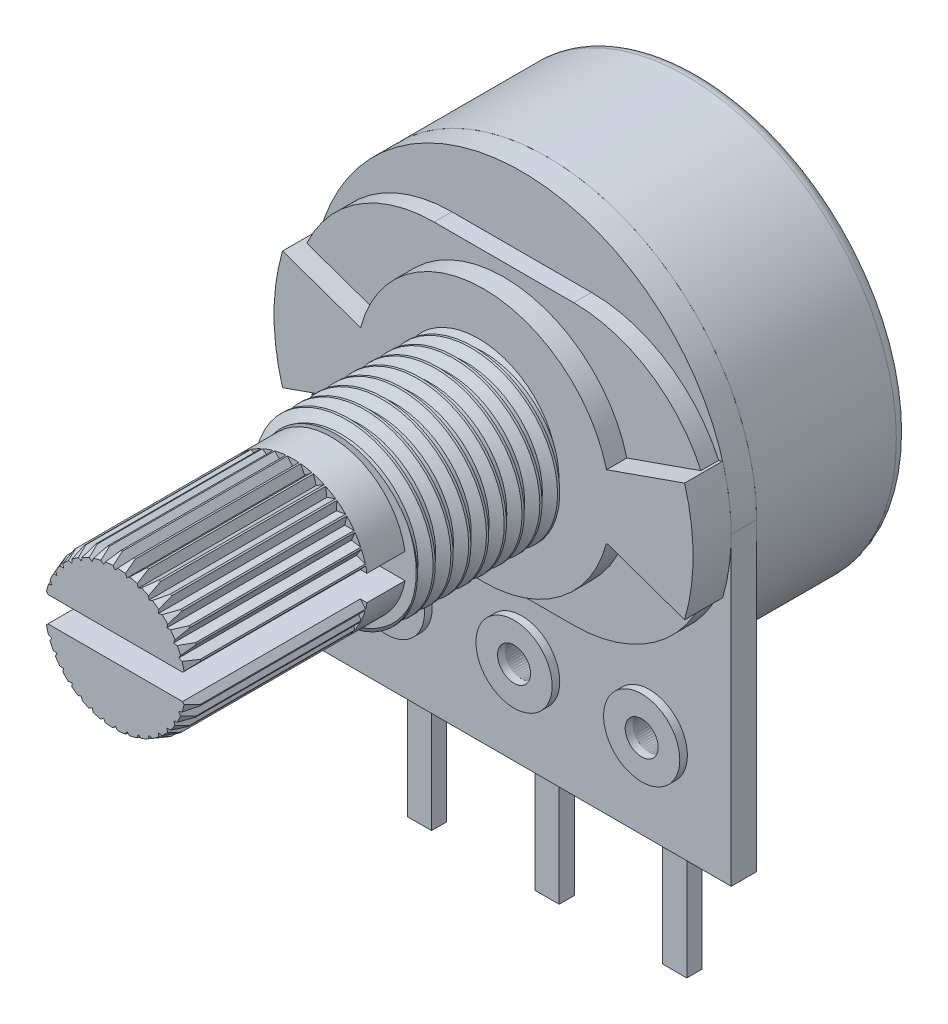
SolidWorks part; units mm, degrees
ref_plane "Front Plane" through (0, 0, 0) normal (0, 0, 1) x (1, 0, 0)
ref_plane "Top Plane" through (0, 0, 0) normal (0, 1, 0) x (1, 0, 0)
ref_plane "Right Plane" through (0, 0, 0) normal (1, 0, 0) x (0, 0, -1)
sketch "Sketch1" plane through (0, 0, 0) normal (0, 0, 1) x (1, 0, 0)
  circle A0 centre (0, 0) radius 8.25
  dimension "D1" = 16.5
extrude "Boss-Extrude1" add sketch "Sketch1" along normal blind 6
sketch "Sketch2" plane through (0, 0, 6) normal (0, 0, 1) x (1, 0, 0)
  line L0 (-8.25, 0) -> (-8.25, -12)
  line L1 (-8.25, -12) -> (8.25, -12)
  line L2 (8.25, -12) -> (8.25, 0)
  circle A1 centre (0, 0) radius 8.25
  arc A2 (8.25, 0) -> (-8.25, 0) centre (0, 0) ccw
  dimension "D2" = 12
  dimension "D1" = 0
extrude "Boss-Extrude2" add sketch "Sketch2" along normal blind 1 separate body
sketch "Sketch3" plane through (0, 0, 6) normal (0, 0, -1) x (-1, 0, 0)
  line L0 (8.25, -12) -> (-8.25, -12) construction
  line L1 (0.475, -12.7) -> (0.475, -17)
  line L2 (-0.475, -12.7) -> (-0.475, -17)
  line L3 (0.3, -6.9) -> (-0.3, -6.9)
  line L4 (0.475, -17) -> (-0.475, -17)
  line L5 (0.475, -12.7) -> (1.8, -12.7)
  line L6 (1.8, -8.4) -> (1.8, -12.7)
  line L7 (5.5, -12.7) -> (5.5, -17)
  line L8 (4.55, -12.7) -> (4.55, -17)
  line L9 (8.25, -12) -> (-8.25, -12) construction
  line L10 (5.325, -6.9) -> (4.725, -6.9)
  line L11 (-1.8, -8.4) -> (-1.8, -12.7)
  line L12 (-0.475, -12.7) -> (-1.8, -12.7)
  line L13 (0, -17) -> (0, -9.9633) construction
  line L14 (0.9971, -13.9354) -> (-0.3886, -13.9354) construction
  line L15 (5.5, -17) -> (4.55, -17)
  line L16 (-1.1375, -10.55) -> (-1.8, -10.55) construction
  line L17 (5.025, -17) -> (5.025, -9.9633) construction
  line L18 (6.0221, -13.9354) -> (4.6364, -13.9354) construction
  line L19 (3.8875, -10.55) -> (3.225, -10.55) construction
  line L20 (1.1375, -12.7) -> (1.1375, -9.9633) construction
  line L21 (1.6718, -10.55) -> (1.8, -10.55) construction
  line L22 (5.5, -12.7) -> (6.825, -12.7)
  line L23 (6.825, -8.4) -> (6.825, -12.7)
  line L24 (6.1625, -12.7) -> (6.1625, -9.9633) construction
  line L25 (6.6968, -10.55) -> (6.825, -10.55) construction
  line L26 (3.8875, -12.7) -> (3.8875, -9.9633) construction
  line L27 (3.225, -8.4) -> (3.225, -12.7)
  line L28 (4.55, -12.7) -> (3.225, -12.7)
  line L29 (-1.1375, -12.7) -> (-1.1375, -9.9633) construction
  line L30 (-4.55, -12.7) -> (-4.55, -17)
  line L33 (-5.5, -12.7) -> (-5.5, -17)
  line L35 (-4.725, -6.9) -> (-5.325, -6.9)
  line L36 (-4.55, -17) -> (-5.5, -17)
  line L37 (-4.55, -12.7) -> (-3.225, -12.7)
  line L38 (-3.225, -8.4) -> (-3.225, -12.7)
  line L39 (-6.825, -8.4) -> (-6.825, -12.7)
  line L40 (-5.5, -12.7) -> (-6.825, -12.7)
  line L41 (-5.025, -17) -> (-5.025, -9.9633) construction
  line L42 (-4.0279, -13.9354) -> (-5.4136, -13.9354) construction
  line L43 (-6.1625, -10.55) -> (-6.825, -10.55) construction
  line L44 (-3.8875, -12.7) -> (-3.8875, -9.9633) construction
  line L45 (-3.3532, -10.55) -> (-3.225, -10.55) construction
  line L46 (-6.1625, -12.7) -> (-6.1625, -9.9633) construction
  arc A0 (3.225, -8.4) -> (4.725, -6.9) centre (4.725, -8.4) cw
  arc A1 (5.325, -6.9) -> (6.825, -8.4) centre (5.325, -8.4) cw
  arc A2 (-1.8, -8.4) -> (-0.3, -6.9) centre (-0.3, -8.4) cw
  arc A3 (0.3, -6.9) -> (1.8, -8.4) centre (0.3, -8.4) cw
  arc A4 (-6.825, -8.4) -> (-5.325, -6.9) centre (-5.325, -8.4) cw
  arc A5 (-4.725, -6.9) -> (-3.225, -8.4) centre (-4.725, -8.4) cw
  circle A6 centre (5.025, -8.4) radius 0.65
  circle A7 centre (0, -8.4) radius 0.65
  circle A8 centre (-5.025, -8.4) radius 0.65
  point P18 (3.225, -6.9)
  point P24 (6.825, -6.9)
  point P34 (3.8875, -10.55)
  point P41 (-1.1375, -10.55)
  point P46 (0, -13.9354)
  point P51 (1.1375, -10.55)
  point P68 (-6.1625, -10.55)
  point P73 (-5.025, -13.9354)
  point P78 (-3.8875, -10.55)
  point P114 (5.025, -13.9354)
  point P176 (6.1625, -10.55)
  dimension "D7" = 1.5
  dimension "D10" = 1.3
  dimension "D1" = 5
  dimension "D3" = 0.7
  dimension "D4" = 0.95
  dimension "D5" = 3.6
  dimension "D6" = 5.1
  dimension "D8" = 11
  dimension "D9" = 3.6
  dimension "D2" = 3
extrude "Boss-Extrude3" add sketch "Sketch3" along normal blind 0.6 separate body
sketch "Sketch4" plane through (0, 0, 7) normal (0, 0, 1) x (1, 0, 0)
  line L0 (0, 0) -> (-8.25, 0) construction
  line L1 (-7.9141, 2.33) -> (-4.8412, 1.25)
  line L2 (-7.9141, -2.33) -> (-4.8412, -1.25)
  line L3 (0, 0) -> (0, 10.6745) construction
  line L4 (7.9141, -2.33) -> (4.8412, -1.25)
  line L5 (7.9141, 2.33) -> (4.8412, 1.25)
  arc A0 (-4.8412, -1.25) -> (4.8412, -1.25) centre (0, 0) ccw
  arc A2 (-7.9141, 2.33) -> (-7.9141, -2.33) centre (0, 0) ccw
  arc A3 (7.9141, 2.33) -> (7.9141, -2.33) centre (0, 0) cw
  arc A4 (4.8412, 1.25) -> (-4.8412, 1.25) centre (0, 0) ccw
  dimension "D1" = 10
  dimension "D2" = 4.66
  dimension "D3" = 2.5
extrude "Boss-Extrude4" add sketch "Sketch4" along normal blind 1.5 separate body
sketch "Sketch15" plane through (0, 0, 7) normal (0, 0, 1) x (1, 0, 0)
  line L0 (2.75, 0) -> (-2.75, 0) construction
  line L1 (2.75, -5.5) -> (-2.75, -5.5)
  line L2 (2.75, 5.5) -> (-2.75, 5.5)
  line L3 (-8.25, 0) -> (-8.25, -12) construction
  arc A0 (2.75, -5.5) -> (2.75, 5.5) centre (2.75, 0) ccw
  arc A1 (-2.75, 5.5) -> (-2.75, -5.5) centre (-2.75, 0) ccw
  point P2 (0, 0)
  dimension "D1" = 11
extrude "Boss-Extrude8" add sketch "Sketch15" along normal blind 0.7
sketch "Sketch5" plane through (0, 0, 8.5) normal (0, 0, 1) x (1, 0, 0)
  circle A0 centre (0, 0) radius 3.35
  dimension "D1" = 6.7
extrude "Boss-Extrude5" add sketch "Sketch5" along normal blind 6
sketch "Sketch6" plane through (0, 0, 14.5) normal (0, 0, 1) x (1, 0, 0)
  line L0 (0, 0) -> (-1.7452, 0) construction
  line L1 (-2.9073, 0.5) -> (2.9073, 0.5)
  line L2 (-2.9073, -0.5) -> (2.9073, -0.5)
  circle A0 centre (0, 0) radius 3.35 construction
  arc A1 (2.9073, 0.5) -> (-2.9073, 0.5) centre (0, 0) ccw
  arc A3 (-2.9073, -0.5) -> (2.9073, -0.5) centre (0, 0) ccw
  dimension "D1" = 5.9
  dimension "D2" = 1
extrude "Boss-Extrude6" add sketch "Sketch6" along normal blind 8.5
thread "Thread1" pitch 0.7 method cut profile "Thread Profile1" start angle 0, offset 1, length 7, pitch 0.7, diameter 6.7
ref_plane "Plane1" through (-3.35, 0, 15.5) normal (0, -1, 0) x (-1, 0, 0)
sketch "Thread Profile1" plane through (-3.35, 0, 15.5) normal (0, -1, 0) x (-1, 0, 0)
  line L0 (0, 0) -> (0, 0.7) construction
  line L11 (0, 0) -> (0, 0.6125)
  line L12 (0, 0.6125) -> (-0.3789, 0.3937)
  line L13 (-0.3789, 0.3937) -> (-0.3789, 0.2187)
  line L15 (-0.3789, 0.2187) -> (0, 0)
  line L17 (-0.3789, 0.3062) -> (0, 0.3062) construction
  point P2 (0, 0)
  dimension "Pitch" = 0.7
  dimension "Profile_Angle" = 60
  dimension "Profile_Land" = 0.175
  dimension "Profile_Height" = 0.3789
chamfer "Chamfer1" distance 0.5 angle 20 2 edges at (0, -2.95, 23) (0, 2.95, 23) first distance on face at (0, -1.725, 18.75) first distance on face at (0, 1.725, 18.75)
sketch "Sketch10" plane through (0, 0, 23) normal (0, 0, 1) x (1, 0, 0)
  line L0 (0, 0) -> (0, 2.95) construction
  line L1 (-0.2382, 2.9681) -> (0, 2.6569)
  line L2 (0, 2.6569) -> (0.255, 2.9668)
  line L3 (0.255, 2.9668) -> (-0.2382, 2.9681)
  line L4 (0.7663, 2.8774) -> (0.2808, 2.9643)
  line L5 (0.4614, 2.6166) -> (0.7663, 2.8774)
  line L6 (0.2808, 2.9643) -> (0.4614, 2.6166)
  line L7 (1.2543, 2.7006) -> (0.7913, 2.8705)
  line L8 (0.9087, 2.4967) -> (1.2543, 2.7006)
  line L9 (0.7913, 2.8705) -> (0.9087, 2.4967)
  line L10 (1.7042, 2.4418) -> (1.2778, 2.6895)
  line L11 (1.3285, 2.301) -> (1.7042, 2.4418)
  line L12 (1.2778, 2.6895) -> (1.3285, 2.301)
  line L13 (2.1024, 2.1088) -> (1.7254, 2.4268)
  line L14 (1.7078, 2.0353) -> (2.1024, 2.1088)
  line L15 (1.7254, 2.4268) -> (1.7078, 2.0353)
  line L16 (2.4366, 1.7117) -> (2.1206, 2.0903)
  line L17 (2.0353, 1.7078) -> (2.4366, 1.7117)
  line L18 (2.1206, 2.0903) -> (2.0353, 1.7078)
  line L19 (2.6968, 1.2626) -> (2.4513, 1.6903)
  line L20 (2.301, 1.3285) -> (2.6968, 1.2626)
  line L21 (2.4513, 1.6903) -> (2.301, 1.3285)
  line L22 (2.8751, 0.7751) -> (2.7076, 1.239)
  line L23 (2.4967, 0.9087) -> (2.8751, 0.7751)
  line L24 (2.7076, 1.239) -> (2.4967, 0.9087)
  line L25 (2.966, 0.2641) -> (2.8816, 0.75)
  line L26 (2.6166, 0.4614) -> (2.966, 0.2641)
  line L27 (2.8816, 0.75) -> (2.6166, 0.4614)
  line L28 (2.9668, -0.255) -> (2.9681, 0.2382)
  line L29 (2.6569, 0) -> (2.9668, -0.255)
  line L30 (2.9681, 0.2382) -> (2.6569, 0)
  line L31 (2.8774, -0.7663) -> (2.9643, -0.2808)
  line L32 (2.6166, -0.4614) -> (2.8774, -0.7663)
  line L33 (2.9643, -0.2808) -> (2.6166, -0.4614)
  line L34 (2.7006, -1.2543) -> (2.8705, -0.7913)
  line L35 (2.4967, -0.9087) -> (2.7006, -1.2543)
  line L36 (2.8705, -0.7913) -> (2.4967, -0.9087)
  line L37 (2.4418, -1.7042) -> (2.6895, -1.2778)
  line L38 (2.301, -1.3285) -> (2.4418, -1.7042)
  line L39 (2.6895, -1.2778) -> (2.301, -1.3285)
  line L40 (2.1088, -2.1024) -> (2.4268, -1.7254)
  line L41 (2.0353, -1.7078) -> (2.1088, -2.1024)
  line L42 (2.4268, -1.7254) -> (2.0353, -1.7078)
  line L43 (1.7117, -2.4366) -> (2.0903, -2.1206)
  line L44 (1.7078, -2.0353) -> (1.7117, -2.4366)
  line L45 (2.0903, -2.1206) -> (1.7078, -2.0353)
  line L46 (1.2626, -2.6968) -> (1.6903, -2.4513)
  line L47 (1.3285, -2.301) -> (1.2626, -2.6968)
  line L48 (1.6903, -2.4513) -> (1.3285, -2.301)
  line L49 (0.7751, -2.8751) -> (1.239, -2.7076)
  line L50 (0.9087, -2.4967) -> (0.7751, -2.8751)
  line L51 (1.239, -2.7076) -> (0.9087, -2.4967)
  line L52 (0.2641, -2.966) -> (0.75, -2.8816)
  line L53 (0.4614, -2.6166) -> (0.2641, -2.966)
  line L54 (0.75, -2.8816) -> (0.4614, -2.6166)
  line L55 (-0.255, -2.9668) -> (0.2382, -2.9681)
  line L56 (0, -2.6569) -> (-0.255, -2.9668)
  line L57 (0.2382, -2.9681) -> (0, -2.6569)
  line L58 (-0.7663, -2.8774) -> (-0.2808, -2.9643)
  line L59 (-0.4614, -2.6166) -> (-0.7663, -2.8774)
  line L60 (-0.2808, -2.9643) -> (-0.4614, -2.6166)
  line L61 (-1.2543, -2.7006) -> (-0.7913, -2.8705)
  line L62 (-0.9087, -2.4967) -> (-1.2543, -2.7006)
  line L63 (-0.7913, -2.8705) -> (-0.9087, -2.4967)
  line L64 (-1.7042, -2.4418) -> (-1.2778, -2.6895)
  line L65 (-1.3285, -2.301) -> (-1.7042, -2.4418)
  line L66 (-1.2778, -2.6895) -> (-1.3285, -2.301)
  line L67 (-2.1024, -2.1088) -> (-1.7254, -2.4268)
  line L68 (-1.7078, -2.0353) -> (-2.1024, -2.1088)
  line L69 (-1.7254, -2.4268) -> (-1.7078, -2.0353)
  line L70 (-2.4366, -1.7117) -> (-2.1206, -2.0903)
  line L71 (-2.0353, -1.7078) -> (-2.4366, -1.7117)
  line L72 (-2.1206, -2.0903) -> (-2.0353, -1.7078)
  line L73 (-2.6968, -1.2626) -> (-2.4513, -1.6903)
  line L74 (-2.301, -1.3285) -> (-2.6968, -1.2626)
  line L75 (-2.4513, -1.6903) -> (-2.301, -1.3285)
  line L76 (-2.8751, -0.7751) -> (-2.7076, -1.239)
  line L77 (-2.4967, -0.9087) -> (-2.8751, -0.7751)
  line L78 (-2.7076, -1.239) -> (-2.4967, -0.9087)
  line L79 (-2.966, -0.2641) -> (-2.8816, -0.75)
  line L80 (-2.6166, -0.4614) -> (-2.966, -0.2641)
  line L81 (-2.8816, -0.75) -> (-2.6166, -0.4614)
  line L82 (-2.9668, 0.255) -> (-2.9681, -0.2382)
  line L83 (-2.6569, 0) -> (-2.9668, 0.255)
  line L84 (-2.9681, -0.2382) -> (-2.6569, 0)
  line L85 (-2.8774, 0.7663) -> (-2.9643, 0.2808)
  line L86 (-2.6166, 0.4614) -> (-2.8774, 0.7663)
  line L87 (-2.9643, 0.2808) -> (-2.6166, 0.4614)
  line L88 (-2.7006, 1.2543) -> (-2.8705, 0.7913)
  line L89 (-2.4967, 0.9087) -> (-2.7006, 1.2543)
  line L90 (-2.8705, 0.7913) -> (-2.4967, 0.9087)
  line L91 (-2.4418, 1.7042) -> (-2.6895, 1.2778)
  line L92 (-2.301, 1.3285) -> (-2.4418, 1.7042)
  line L93 (-2.6895, 1.2778) -> (-2.301, 1.3285)
  line L94 (-2.1088, 2.1024) -> (-2.4268, 1.7254)
  line L95 (-2.0353, 1.7078) -> (-2.1088, 2.1024)
  line L96 (-2.4268, 1.7254) -> (-2.0353, 1.7078)
  line L97 (-1.7117, 2.4366) -> (-2.0903, 2.1206)
  line L98 (-1.7078, 2.0353) -> (-1.7117, 2.4366)
  line L99 (-2.0903, 2.1206) -> (-1.7078, 2.0353)
  line L100 (-1.2626, 2.6968) -> (-1.6903, 2.4513)
  line L101 (-1.3285, 2.301) -> (-1.2626, 2.6968)
  line L102 (-1.6903, 2.4513) -> (-1.3285, 2.301)
  line L103 (-0.7751, 2.8751) -> (-1.239, 2.7076)
  line L104 (-0.9087, 2.4967) -> (-0.7751, 2.8751)
  line L105 (-1.239, 2.7076) -> (-0.9087, 2.4967)
  line L106 (-0.2641, 2.966) -> (-0.75, 2.8816)
  line L107 (-0.4614, 2.6166) -> (-0.2641, 2.966)
  line L108 (-0.75, 2.8816) -> (-0.4614, 2.6166)
  arc A0 (2.9073, 0.5) -> (-2.9073, 0.5) centre (0, 0) ccw construction
  point P116 (0, 0)
  dimension "D1" = 36
extrude "Cut-Extrude2" cut sketch "Sketch10" against normal blind 7
sketch "Sketch16" plane through (0, 0, 0) normal (0, 0, -1) x (-1, 0, 0)
  line L0 (0, 0) -> (9.7747, 0) construction
  line L2 (6.5, 1) -> (10.1552, 1)
  line L3 (6.5, 1) -> (6.5, -1)
  line L4 (6.5, -1) -> (10.1552, -1)
  line L5 (10.1552, 1) -> (10.1552, -1)
  line L6 (8.3276, -1) -> (8.3276, 1) construction
  line L7 (6.5, 0) -> (10.1552, 0) construction
  point P7 (8.25, 0)
  point P103 (8.3276, 0)
  dimension "D1" = 1.75
  dimension "D2" = 2
extrude "Cut-Extrude5" cut sketch "Sketch16" against normal blind 2.75
fillet "Fillet1" radius 0.5 3 edges at (-8.25, 0, 2.75) (-6.5, 0, 0) (8.25, 0, 0)
shell "Shell2" thickness 0.5 removed face at (8.25, 0, 6) removed face at (-7.2943, -1, 1.3496) removed face at (-7.2943, 1, 1.3496)
sketch "Sketch12" plane through (0, 0, 6) normal (0, 0, -1) x (-1, 0, 0)
  line L0 (-6.0208, -6) -> (6.0208, -6)
  arc A0 (-6.0208, -6) -> (6.0208, -6) centre (0, 0) ccw
  dimension "D2" = 8.5
  dimension "D1" = 6
extrude "Cut-Extrude3" cut sketch "Sketch12" along normal blind 2
sketch "Sketch13" plane through (0, 0, 6) normal (0, 0, -1) x (-1, 0, 0)
  circle A0 centre (-5.025, -8.4) radius 0.65
  circle A1 centre (0, -8.4) radius 0.65
  circle A2 centre (5.025, -8.4) radius 0.65
  circle A3 centre (-5.025, -8.4) radius 0.65 construction
  circle A4 centre (0, -8.4) radius 0.65 construction
  circle A5 centre (5.025, -8.4) radius 0.65 construction
  dimension "D1" = 1.3
extrude "Cut-Extrude4" cut sketch "Sketch13" against normal blind 2
sketch "Sketch14" plane through (0, 0, 7) normal (0, 0, 1) x (1, 0, 0)
  circle A0 centre (-5.025, -8.4) radius 1.5
  circle A1 centre (0, -8.4) radius 1.5
  circle A2 centre (5.025, -8.4) radius 1.5
  circle A3 centre (5.025, -8.4) radius 0.65 construction
  circle A4 centre (0, -8.4) radius 0.65 construction
  circle A5 centre (-5.025, -8.4) radius 0.65 construction
  circle A6 centre (5.025, -8.4) radius 0.65
  circle A7 centre (0, -8.4) radius 0.65
  circle A8 centre (-5.025, -8.4) radius 0.65
  dimension "D1" = 3
extrude "Boss-Extrude7" add sketch "Sketch14" along normal blind 0.3 and the other way up to surface other way up to face at (-5.025, -11.4779, 5.4)
